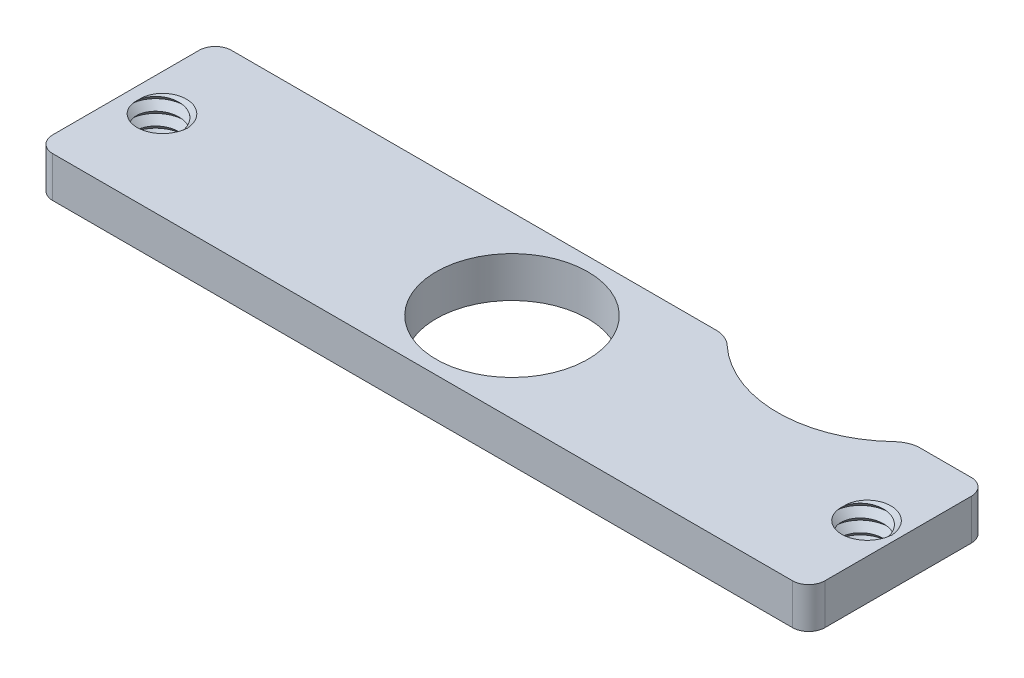
SolidWorks part; units mm, degrees
ref_plane "Front Plane" through (0, 0, 0) normal (0, 0, 1) x (1, 0, 0)
ref_plane "Top Plane" through (0, 0, 0) normal (0, 1, 0) x (1, 0, 0)
ref_plane "Right Plane" through (0, 0, 0) normal (1, 0, 0) x (0, 0, -1)
sketch "Sketch1" plane through (0, 0, 0) normal (0, 1, 0) x (1, 0, 0)
  line L0 (-90.4875, 0) -> (-82.55, 0) construction
  line L1 (-90.4875, -20.955) -> (90.4875, -20.955)
  line L2 (-90.4875, -20.955) -> (-90.4875, 20.955)
  line L3 (-90.4875, 20.955) -> (90.4875, 20.955)
  line L4 (90.4875, -20.955) -> (90.4875, 20.955)
  line L5 (-90.4875, -20.955) -> (90.4875, 20.955) construction
  line L6 (-90.4875, 20.955) -> (90.4875, -20.955) construction
  line L7 (0, 20.955) -> (0, -20.955) construction
  line L8 (90.4875, 0) -> (82.55, 0) construction
  line L9 (0, 20.955) -> (0, 40.005) construction
  line L10 (0, 40.005) -> (50.8, 40.005) construction
  circle A2 centre (0, 0) radius 17.78
  circle A3 centre (-82.55, 0) radius 5
  circle A4 centre (82.55, 0) radius 5
  arc A5 (29.5015, 20.955) -> (72.0985, 20.955) centre (50.8, 40.005) ccw
  point P0 (0, 0)
  dimension "D3" = 7.9375
  dimension "D4" = 35.56
  dimension "D5" = 10
  dimension "D8" = 57.15
  dimension "D1" = 180.975
  dimension "D2" = 41.91
  dimension "D6" = 19.05
  dimension "D7" = 50.8
extrude "Boss-Extrude1" add sketch "Sketch1" along normal blind 9.525 contours L1 L4 L3 L2 A4 A3 A2
sketch "Sketch3" plane through (0, 9.525, 0) normal (0, 1, 0) x (1, 0, 0)
  circle A0 centre (-82.55, 0) radius 5 construction
  circle A1 centre (-82.55, 0) radius 5
curve "Helix/Spiral1" pitch 3 height 15 turns 5
sketch "Sketch4" plane through (0, 9.525, 0) normal (0, 1, 0) x (1, 0, 0)
  circle A0 centre (82.55, 0) radius 5 construction
  circle A1 centre (82.55, 0) radius 5
curve "Helix/Spiral2" pitch 3 height 15 turns 5
sketch "Sketch5" plane through (0, 0, 0) normal (0, 0, 1) x (1, 0, 0)
  line L0 (-82.55, 9.525) -> (-87.55, 9.525) construction
  line L5 (-87.55, 9.525) -> (-87.55, 12.524)
  line L6 (-87.55, 11.0245) -> (-99.6948, 11.0245) construction
  line L7 (-87.55, 12.524) -> (-89.0495, 11.0245)
  line L8 (-89.0495, 11.0245) -> (-87.55, 9.525)
  spline S0 degree 3 poles (-2082.224, -16.8914) (14.7395, 13.7566) (-66.4399, 11.374) (-86.1771, 9.15) (-87.2898, 8.9625) (-87.6801, 8.775) (-87.2897, 8.5875) (-86.1776, 8.4) (-83.9585, 8.15) (-81.1416, 7.9) (-78.9224, 7.65) (-77.8103, 7.4625) (-77.4198, 7.275) (-77.8103, 7.0875) (-78.9224, 6.9) (-81.1416, 6.65) (-83.9584, 6.4) (-86.1776, 6.15) (-87.2897, 5.9625) (-87.6802, 5.775) (-87.2897, 5.5875) (-86.1776, 5.4) (-83.9584, 5.15) (-81.1416, 4.9) (-78.9224, 4.65) (-77.8103, 4.4625) (-77.4198, 4.275) (-77.8103, 4.0875) (-78.9224, 3.9) (-81.1416, 3.65) (-83.9584, 3.4) (-86.1776, 3.15) (-87.2897, 2.9625) (-87.6802, 2.775) (-87.2897, 2.5875) (-86.1776, 2.4) (-83.9584, 2.15) (-81.1416, 1.9) (-78.9224, 1.65) (-77.8103, 1.4625) (-77.4198, 1.275) (-77.8103, 1.0875) (-78.9224, 0.9) (-81.1416, 0.65) (-83.9584, 0.4) (-86.1776, 0.15) (-87.2897, -0.0375) (-87.6802, -0.225) (-87.2897, -0.4125) (-86.1776, -0.6) (-83.9584, -0.85) (-81.1416, -1.1) (-78.9224, -1.35) (-77.8103, -1.5375) (-77.4198, -1.725) (-77.8103, -1.9125) (-78.9224, -2.1) (-81.1416, -2.35) (-83.9584, -2.6) (-86.1776, -2.85) (-87.2897, -3.0375) (-87.6802, -3.225) (-87.2897, -3.4125) (-86.1776, -3.6) (-83.9584, -3.85) (-81.1415, -4.1) (-78.9224, -4.35) (-77.8103, -4.5375) (-77.4199, -4.725) (-77.8102, -4.9125) (-78.9229, -5.1) (-98.6599, -7.324) (-179.8384, -9.7065) (1917.0793, 20.9407) knots -0.407845 -0.407845 -0.407845 -0.407845 0.0125 0.025 0.0375 0.05 0.0625 0.075 0.0875 0.1125 0.125 0.1375 0.15 0.1625 0.175 0.1875 0.2125 0.225 0.2375 0.25 0.2625 0.275 0.2875 0.3125 0.325 0.3375 0.35 0.3625 0.375 0.3875 0.4125 0.425 0.4375 0.45 0.4625 0.475 0.4875 0.5125 0.525 0.5375 0.55 0.5625 0.575 0.5875 0.6125 0.625 0.6375 0.65 0.6625 0.675 0.6875 0.7125 0.725 0.7375 0.75 0.7625 0.775 0.7875 0.8125 0.825 0.8375 0.85 0.8625 0.875 0.8875 0.9125 0.925 0.9375 0.95 0.9625 0.975 0.9875 1.407842 1.407842 1.407842 1.407842 only from (-82.55, 9.525) to (-82.55, -5.475) construction
  spline S1 degree 3 poles (-82.55, 9.525) (-83.2003, 9.4629) (-84.5151, 9.3373) (-86.1771, 9.15) (-87.2898, 8.9625) (-87.6801, 8.775) (-87.2897, 8.5875) (-86.1776, 8.4) (-83.9585, 8.15) (-81.1416, 7.9) (-78.9224, 7.65) (-77.8103, 7.4625) (-77.4198, 7.275) (-77.8103, 7.0875) (-78.9224, 6.9) (-81.1416, 6.65) (-83.9584, 6.4) (-86.1776, 6.15) (-87.2897, 5.9625) (-87.6802, 5.775) (-87.2897, 5.5875) (-86.1776, 5.4) (-83.9584, 5.15) (-81.1416, 4.9) (-78.9224, 4.65) (-77.8103, 4.4625) (-77.4198, 4.275) (-77.8103, 4.0875) (-78.9224, 3.9) (-81.1416, 3.65) (-83.9584, 3.4) (-86.1776, 3.15) (-87.2897, 2.9625) (-87.6802, 2.775) (-87.2897, 2.5875) (-86.1776, 2.4) (-83.9584, 2.15) (-81.1416, 1.9) (-78.9224, 1.65) (-77.8103, 1.4625) (-77.4198, 1.275) (-77.8103, 1.0875) (-78.9224, 0.9) (-81.1416, 0.65) (-83.9584, 0.4) (-86.1776, 0.15) (-87.2897, -0.0375) (-87.6802, -0.225) (-87.2897, -0.4125) (-86.1776, -0.6) (-83.9584, -0.85) (-81.1416, -1.1) (-78.9224, -1.35) (-77.8103, -1.5375) (-77.4198, -1.725) (-77.8103, -1.9125) (-78.9224, -2.1) (-81.1416, -2.35) (-83.9584, -2.6) (-86.1776, -2.85) (-87.2897, -3.0375) (-87.6802, -3.225) (-87.2897, -3.4125) (-86.1776, -3.6) (-83.9584, -3.85) (-81.1415, -4.1) (-78.9224, -4.35) (-77.8103, -4.5375) (-77.4199, -4.725) (-77.8102, -4.9125) (-78.9229, -5.1) (-80.5849, -5.2873) (-81.8997, -5.4129) (-82.55, -5.475) knots 0 0 0 0 0.0125 0.025 0.0375 0.05 0.0625 0.075 0.0875 0.1125 0.125 0.1375 0.15 0.1625 0.175 0.1875 0.2125 0.225 0.2375 0.25 0.2625 0.275 0.2875 0.3125 0.325 0.3375 0.35 0.3625 0.375 0.3875 0.4125 0.425 0.4375 0.45 0.4625 0.475 0.4875 0.5125 0.525 0.5375 0.55 0.5625 0.575 0.5875 0.6125 0.625 0.6375 0.65 0.6625 0.675 0.6875 0.7125 0.725 0.7375 0.75 0.7625 0.775 0.7875 0.8125 0.825 0.8375 0.85 0.8625 0.875 0.8875 0.9125 0.925 0.9375 0.95 0.9625 0.975 0.9875 1 1 1 1 construction
  dimension "D1" = 2.999
sweep "Cut-Sweep1" cut profiles "Sketch5" path "Helix/Spiral1" align with end faces yes
sketch "Sketch7" plane through (0, 0, 0) normal (0, 0, 1) x (1, 0, 0)
  line L0 (82.55, 9.525) -> (77.55, 9.525) construction
  line L3 (76.0505, 11.0245) -> (77.55, 9.525)
  line L5 (77.55, 9.525) -> (77.55, 12.524)
  line L6 (77.55, 11.0245) -> (83.8771, 11.0245) construction
  line L7 (77.55, 12.524) -> (76.0505, 11.0245)
  spline S0 degree 3 poles (-1917.124, -16.8914) (179.8395, 13.7566) (98.6601, 11.374) (78.9229, 9.15) (77.8102, 8.9625) (77.4199, 8.775) (77.8103, 8.5875) (78.9224, 8.4) (81.1415, 8.15) (83.9584, 7.9) (86.1776, 7.65) (87.2897, 7.4625) (87.6802, 7.275) (87.2897, 7.0875) (86.1776, 6.9) (83.9584, 6.65) (81.1416, 6.4) (78.9224, 6.15) (77.8103, 5.9625) (77.4198, 5.775) (77.8103, 5.5875) (78.9224, 5.4) (81.1416, 5.15) (83.9584, 4.9) (86.1776, 4.65) (87.2897, 4.4625) (87.6802, 4.275) (87.2897, 4.0875) (86.1776, 3.9) (83.9584, 3.65) (81.1416, 3.4) (78.9224, 3.15) (77.8103, 2.9625) (77.4198, 2.775) (77.8103, 2.5875) (78.9224, 2.4) (81.1416, 2.15) (83.9584, 1.9) (86.1776, 1.65) (87.2897, 1.4625) (87.6802, 1.275) (87.2897, 1.0875) (86.1776, 0.9) (83.9584, 0.65) (81.1416, 0.4) (78.9224, 0.15) (77.8103, -0.0375) (77.4198, -0.225) (77.8103, -0.4125) (78.9224, -0.6) (81.1416, -0.85) (83.9584, -1.1) (86.1776, -1.35) (87.2897, -1.5375) (87.6802, -1.725) (87.2897, -1.9125) (86.1776, -2.1) (83.9584, -2.35) (81.1416, -2.6) (78.9224, -2.85) (77.8103, -3.0375) (77.4198, -3.225) (77.8103, -3.4125) (78.9224, -3.6) (81.1416, -3.85) (83.9585, -4.1) (86.1776, -4.35) (87.2897, -4.5375) (87.6801, -4.725) (87.2898, -4.9125) (86.1771, -5.1) (66.4401, -7.324) (-14.7384, -9.7065) (2082.1793, 20.9407) knots -0.407845 -0.407845 -0.407845 -0.407845 0.0125 0.025 0.0375 0.05 0.0625 0.075 0.0875 0.1125 0.125 0.1375 0.15 0.1625 0.175 0.1875 0.2125 0.225 0.2375 0.25 0.2625 0.275 0.2875 0.3125 0.325 0.3375 0.35 0.3625 0.375 0.3875 0.4125 0.425 0.4375 0.45 0.4625 0.475 0.4875 0.5125 0.525 0.5375 0.55 0.5625 0.575 0.5875 0.6125 0.625 0.6375 0.65 0.6625 0.675 0.6875 0.7125 0.725 0.7375 0.75 0.7625 0.775 0.7875 0.8125 0.825 0.8375 0.85 0.8625 0.875 0.8875 0.9125 0.925 0.9375 0.95 0.9625 0.975 0.9875 1.407842 1.407842 1.407842 1.407842 only from (82.55, 9.525) to (82.55, -5.475) construction
  spline S1 degree 3 poles (82.55, 9.525) (81.8997, 9.4629) (80.5849, 9.3373) (78.9229, 9.15) (77.8102, 8.9625) (77.4199, 8.775) (77.8103, 8.5875) (78.9224, 8.4) (81.1415, 8.15) (83.9584, 7.9) (86.1776, 7.65) (87.2897, 7.4625) (87.6802, 7.275) (87.2897, 7.0875) (86.1776, 6.9) (83.9584, 6.65) (81.1416, 6.4) (78.9224, 6.15) (77.8103, 5.9625) (77.4198, 5.775) (77.8103, 5.5875) (78.9224, 5.4) (81.1416, 5.15) (83.9584, 4.9) (86.1776, 4.65) (87.2897, 4.4625) (87.6802, 4.275) (87.2897, 4.0875) (86.1776, 3.9) (83.9584, 3.65) (81.1416, 3.4) (78.9224, 3.15) (77.8103, 2.9625) (77.4198, 2.775) (77.8103, 2.5875) (78.9224, 2.4) (81.1416, 2.15) (83.9584, 1.9) (86.1776, 1.65) (87.2897, 1.4625) (87.6802, 1.275) (87.2897, 1.0875) (86.1776, 0.9) (83.9584, 0.65) (81.1416, 0.4) (78.9224, 0.15) (77.8103, -0.0375) (77.4198, -0.225) (77.8103, -0.4125) (78.9224, -0.6) (81.1416, -0.85) (83.9584, -1.1) (86.1776, -1.35) (87.2897, -1.5375) (87.6802, -1.725) (87.2897, -1.9125) (86.1776, -2.1) (83.9584, -2.35) (81.1416, -2.6) (78.9224, -2.85) (77.8103, -3.0375) (77.4198, -3.225) (77.8103, -3.4125) (78.9224, -3.6) (81.1416, -3.85) (83.9585, -4.1) (86.1776, -4.35) (87.2897, -4.5375) (87.6801, -4.725) (87.2898, -4.9125) (86.1771, -5.1) (84.5151, -5.2873) (83.2003, -5.4129) (82.55, -5.475) knots 0 0 0 0 0.0125 0.025 0.0375 0.05 0.0625 0.075 0.0875 0.1125 0.125 0.1375 0.15 0.1625 0.175 0.1875 0.2125 0.225 0.2375 0.25 0.2625 0.275 0.2875 0.3125 0.325 0.3375 0.35 0.3625 0.375 0.3875 0.4125 0.425 0.4375 0.45 0.4625 0.475 0.4875 0.5125 0.525 0.5375 0.55 0.5625 0.575 0.5875 0.6125 0.625 0.6375 0.65 0.6625 0.675 0.6875 0.7125 0.725 0.7375 0.75 0.7625 0.775 0.7875 0.8125 0.825 0.8375 0.85 0.8625 0.875 0.8875 0.9125 0.925 0.9375 0.95 0.9625 0.975 0.9875 1 1 1 1 construction
  point P6 (77.55, 9.525)
  dimension "D1" = 2.999
  dimension "D2" = 45
sweep "Cut-Sweep3" cut profiles "Sketch7" path "Helix/Spiral2" align with end faces yes
fillet "Fillet1" radius 6.35 2 edges at (29.5015, 4.7625, -20.955) (72.0985, 4.7625, -20.955)
fillet "Fillet2" radius 3.81 4 edges at (-90.4875, 4.7625, -20.955) (90.4875, 4.7625, -20.955) (90.4875, 4.7625, 20.955) (-90.4875, 4.7625, 20.955)
